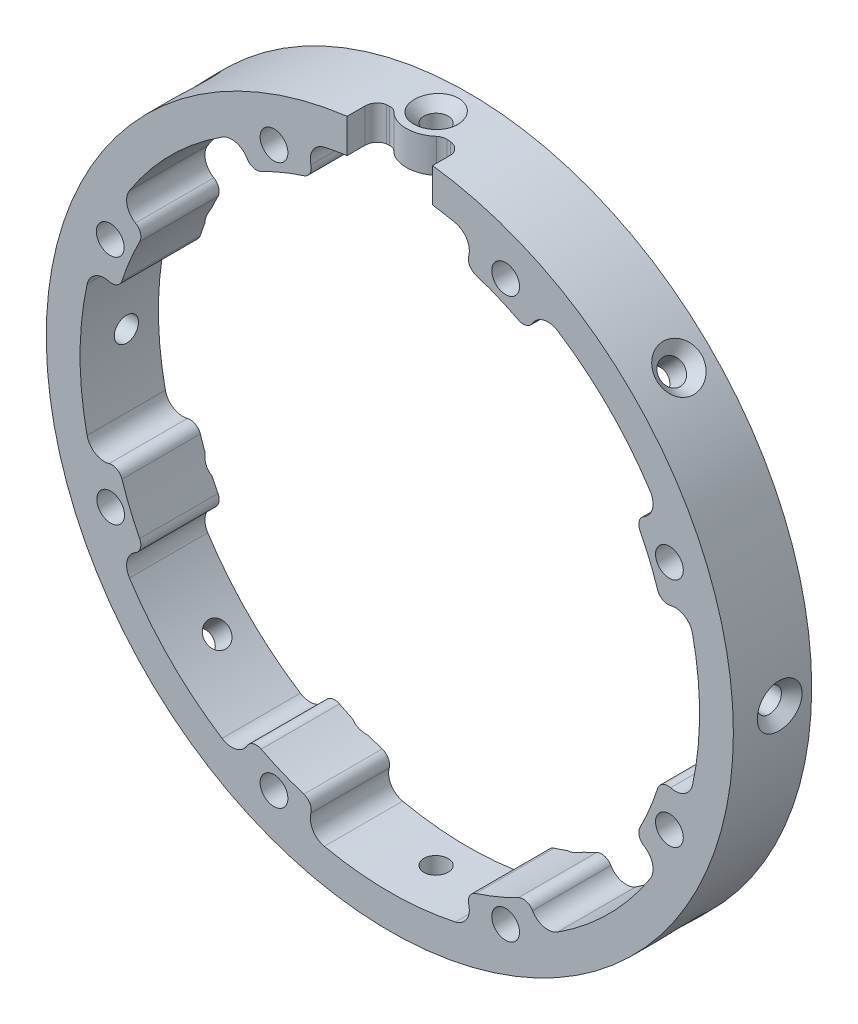
SolidWorks part; units mm, degrees
ref_plane "前视基准面" through (0, 0, 0) normal (0, 0, 1) x (1, 0, 0)
ref_plane "上视基准面" through (0, 0, 0) normal (0, 1, 0) x (1, 0, 0)
ref_plane "右视基准面" through (0, 0, 0) normal (1, 0, 0) x (0, 0, -1)
sketch "草图1" plane through (0, 0, 0) normal (0, 0, 1) x (1, 0, 0)
  line L0 (11.1292, 41.5348) -> (10.0939, 37.6711)
  line L17 (21.5, 37.2391) -> (19.5, 33.775)
  line L18 (-11.1292, 41.5348) -> (-10.0939, 37.6711)
  line L19 (37.2391, 21.5) -> (33.775, 19.5)
  line L20 (41.5348, 11.1292) -> (37.6711, 10.0939)
  line L21 (41.5348, -11.1292) -> (37.6711, -10.0939)
  line L22 (37.2391, -21.5) -> (33.775, -19.5)
  line L23 (21.5, -37.2391) -> (19.5, -33.775)
  line L24 (11.1292, -41.5348) -> (10.0939, -37.6711)
  line L25 (-11.1292, -41.5348) -> (-10.0939, -37.6711)
  line L26 (-21.5, -37.2391) -> (-19.5, -33.775)
  line L27 (-37.2391, -21.5) -> (-33.775, -19.5)
  line L28 (-41.5348, -11.1292) -> (-37.6711, -10.0939)
  line L29 (-41.5348, 11.1292) -> (-37.6711, 10.0939)
  line L30 (-37.2391, 21.5) -> (-33.775, 19.5)
  line L31 (-21.5, 37.2391) -> (-19.5, 33.775)
  circle A1 centre (0, 0) radius 48.25
  arc A3 (10.0939, 37.6711) -> (19.5, 33.775) centre (0, 0) cw
  arc A4 (11.1292, 41.5348) -> (-11.1292, 41.5348) centre (0, 0) ccw
  arc A21 (37.2391, 21.5) -> (21.5, 37.2391) centre (0, 0) ccw
  arc A22 (33.775, 19.5) -> (37.6711, 10.0939) centre (0, 0) cw
  arc A23 (41.5348, -11.1292) -> (41.5348, 11.1292) centre (0, 0) ccw
  arc A24 (37.6711, -10.0939) -> (33.775, -19.5) centre (0, 0) cw
  arc A25 (21.5, -37.2391) -> (37.2391, -21.5) centre (0, 0) ccw
  arc A26 (19.5, -33.775) -> (10.0939, -37.6711) centre (0, 0) cw
  arc A27 (-11.1292, -41.5348) -> (11.1292, -41.5348) centre (0, 0) ccw
  arc A28 (-10.0939, -37.6711) -> (-19.5, -33.775) centre (0, 0) cw
  arc A29 (-37.2391, -21.5) -> (-21.5, -37.2391) centre (0, 0) ccw
  arc A30 (-33.775, -19.5) -> (-37.6711, -10.0939) centre (0, 0) cw
  arc A31 (-41.5348, 11.1292) -> (-41.5348, -11.1292) centre (0, 0) ccw
  arc A32 (-37.6711, 10.0939) -> (-33.775, 19.5) centre (0, 0) cw
  arc A33 (-21.5, 37.2391) -> (-37.2391, 21.5) centre (0, 0) ccw
  arc A34 (-19.5, 33.775) -> (-10.0939, 37.6711) centre (0, 0) cw
  point P51 (0, 0)
  point P56 (0, 0)
  dimension "D1" = 8
  dimension "D2" = 43
  dimension "D3" = 96.5
extrude "凸台-拉伸1" add sketch "草图1" against normal blind 11
hole_wizard "M3 锥坑平头的锥孔2" positions "3D草图3" profile "草图4" countersink size "M3" standard "BSI" end condition through all
sketch3d "3D草图3"
  point P67 (34.1179, 34.1179, -6.5)
  point P76 (48.25, 0, -6.5)
  point P83 (34.1179, -34.1179, -6.5)
  point P85 (-34.1179, 34.1179, -6.5)
  point P87 (-34.1179, -34.1179, -6.5)
  point P96 (0, -48.25, -6.5)
  point P98 (0, 48.25, -6.5)
  point P105 (-48.25, 0, -6.5)
sketch "草图4" plane through (34.1179, 34.1179, -6.5) normal (0, 0, 1) x (-0.7071, 0.7071, 0)
  line L0 (0, 0) -> (0, 116.4858)
  line L1 (0, 116.4858) -> (1.7, 116.4858)
  line L2 (1.7, 116.4858) -> (1.7, 1.45)
  line L3 (1.7, 1.45) -> (3.15, 0)
  line L5 (3.15, 0) -> (0, 0)
  line L6 (-1.7, 1.45) -> (-3.15, 0) construction
  line L11 (0, -6.35) -> (0, 107.95) construction
  dimension "通孔孔直径" = 3.4
  dimension "通孔孔深度" = 116.4858
  dimension "近端锥形沉头孔直径" = 6.3
  dimension "近端锥形沉头孔角度" = 90
ref_plane "基准面1" through (0, 48.25, 0) normal (0, 1, 0) x (1, 0, 0)
sketch "草图7" plane through (0, 48.25, 0) normal (0, 1, 0) x (1, 0, 0)
  line L0 (-6, 0) -> (6, 0)
  line L1 (-48.25, 0) -> (48.25, 0) construction
  line L2 (6, 0) -> (6, 4)
  line L3 (6, 4) -> (3.3749, 4)
  line L5 (-6, 0) -> (-6, 4)
  line L6 (-6, 4) -> (-3.3749, 4)
  arc A1 (3.3749, 4) -> (-3.3749, 4) centre (0, 6.5) cw
extrude "切除-拉伸1" cut sketch "草图7" against normal up to next
sketch "草图9" plane through (0, 0, 0) normal (0, 0, 1) x (1, 0, 0)
  line L0 (0, 0) -> (0, 43) construction
  line L1 (0, 0) -> (16.264, 39.2649) construction
  circle A0 centre (0, 0) radius 42.5 construction
  circle A1 centre (16.264, 39.2649) radius 2
  arc A2 (3.3749, 42.8674) -> (-3.3749, 42.8674) centre (0, 0) ccw construction
  circle A3 centre (39.2649, 16.264) radius 2
  circle A4 centre (39.2649, -16.264) radius 2
  circle A5 centre (16.264, -39.2649) radius 2
  circle A6 centre (-16.264, -39.2649) radius 2
  circle A7 centre (-39.2649, -16.264) radius 2
  circle A8 centre (-39.2649, 16.264) radius 2
  circle A9 centre (-16.264, 39.2649) radius 2
  point P25 (0, 0)
  dimension "D1" = 85
  dimension "D3" = 4
  dimension "D2" = 22.5
  dimension "D4" = 8
hole_wizard "打孔尺寸(%根据十字)槽半沉头木螺钉的类型2" positions "3D草图4" profile "草图8" countersink size "M3.5" standard "GB" end condition up to next
sketch3d "3D草图4"
  point P13 (39.2649, 16.264, -11)
  point P19 (16.264, 39.2649, -11)
  point P21 (-16.264, 39.2649, -11)
  point P23 (39.2649, -16.264, -11)
  point P26 (-39.2649, 16.264, -11)
  point P28 (-39.2044, -16.264, -11)
  point P30 (-16.264, -39.2649, -11)
  point P32 (16.264, -39.2649, -11)
sketch "草图8" plane through (39.2649, 16.264, -11) normal (1, 0, 0) x (0, 1, 0)
  line L0 (0, 0) -> (0, 11)
  line L1 (0, 11) -> (1.95, 11)
  line L2 (1.95, 11) -> (1.95, 1.3)
  line L3 (1.95, 1.3) -> (3.25, 0)
  line L5 (3.25, 0) -> (0, 0)
  line L6 (-1.95, 1.3) -> (-3.25, 0) construction
  line L11 (0, -6.35) -> (0, 107.95) construction
  dimension "通孔孔直径" = 3.9
  dimension "通孔孔深度" = 11
  dimension "近端锥形沉头孔直径" = 6.5
  dimension "近端锥形沉头孔角度" = 90
fillet "圆角1" radius 2 32 edges at (-41.5348, -11.1292, -5.5) (-37.6711, -10.0939, -5.5) (-33.775, -19.5, -5.5) (-37.2391, -21.5, -5.5) (-21.5, -37.2391, -5.5) (-10.0939, -37.6711, -5.5) (-19.5, -33.775, -5.5) (-11.1292, -41.5348, -5.5) (11.1292, -41.5348, -5.5) (10.0939, -37.6711, -5.5) (19.5, -33.775, -5.5) (21.5, -37.2391, -5.5) (37.2391, -21.5, -5.5) (33.775, -19.5, -5.5) (37.6711, -10.0939, -5.5) (41.5348, -11.1292, -5.5) (41.5348, 11.1292, -5.5) (37.6711, 10.0939, -5.5) (33.775, 19.5, -5.5) (37.2391, 21.5, -5.5) (21.5, 37.2391, -5.5) (11.1292, 41.5348, -5.5) (10.0939, 37.6711, -5.5) (19.5, 33.775, -5.5) (-11.1292, 41.5348, -5.5) (-10.0939, 37.6711, -5.5) (-21.5, 37.2391, -5.5) (-19.5, 33.775, -5.5) (-37.2391, 21.5, -5.5) (-33.775, 19.5, -5.5) (-37.6711, 10.0939, -5.5) (-41.5348, 11.1292, -5.5)
fillet "圆角2" radius 1.5 4 edges at (-6, 45.2274, -4) (6, 45.2274, -4) (-3.3749, 45.4996, -4) (3.3749, 45.4996, -4)
sketch "草图10" plane through (0, 0, 0) normal (0, 0, 1) x (1, 0, 0)
  line L0 (6.5, 47.8755) -> (6.5, 43.0116)
  line L1 (-6.5, 43.0116) -> (-6.5, 47.8755)
  line L2 (-6, 42.5793) -> (-6, 47.8755)
  line L3 (6, 47.8755) -> (6, 42.5793)
  line L4 (-6, 42.5793) -> (-6, 47.8755)
  line L5 (6, 47.8755) -> (6, 42.5793)
  arc A0 (9.1956, 42.517) -> (6.5, 43.0116) centre (0, 0) ccw
  arc A1 (11.0819, 39.4264) -> (9.1956, 42.517) centre (8.6671, 40.0735) ccw
  arc A2 (11.0819, 39.4264) -> (12.0724, 37.6099) centre (12.5308, 39.0382) ccw
  arc A3 (18.0578, 35.1307) -> (12.0724, 37.6099) centre (0, 0) ccw
  arc A4 (18.0578, 35.1307) -> (20.0426, 35.7148) centre (18.7435, 36.4648) ccw
  arc A5 (23.5618, 36.5663) -> (20.0426, 35.7148) centre (22.2076, 34.4648) ccw
  arc A6 (36.5663, 23.5618) -> (23.5618, 36.5663) centre (0, 0) ccw
  arc A7 (35.7148, 20.0426) -> (36.5663, 23.5618) centre (34.4648, 22.2076) ccw
  arc A8 (35.7148, 20.0426) -> (35.1307, 18.0578) centre (36.4648, 18.7435) ccw
  arc A9 (37.6099, 12.0724) -> (35.1307, 18.0578) centre (0, 0) ccw
  arc A10 (37.6099, 12.0724) -> (39.4264, 11.0819) centre (39.0382, 12.5308) ccw
  arc A11 (42.517, 9.1956) -> (39.4264, 11.0819) centre (40.0735, 8.6671) ccw
  arc A12 (42.517, -9.1956) -> (42.517, 9.1956) centre (0, 0) ccw
  arc A13 (39.4264, -11.0819) -> (42.517, -9.1956) centre (40.0735, -8.6671) ccw
  arc A14 (39.4264, -11.0819) -> (37.6099, -12.0724) centre (39.0382, -12.5308) ccw
  arc A15 (35.1307, -18.0578) -> (37.6099, -12.0724) centre (0, 0) ccw
  arc A16 (35.1307, -18.0578) -> (35.7148, -20.0426) centre (36.4648, -18.7435) ccw
  arc A17 (36.5663, -23.5618) -> (35.7148, -20.0426) centre (34.4648, -22.2076) ccw
  arc A18 (23.5618, -36.5663) -> (36.5663, -23.5618) centre (0, 0) ccw
  arc A19 (20.0426, -35.7148) -> (23.5618, -36.5663) centre (22.2076, -34.4648) ccw
  arc A20 (20.0426, -35.7148) -> (18.0578, -35.1307) centre (18.7435, -36.4648) ccw
  arc A21 (12.0724, -37.6099) -> (18.0578, -35.1307) centre (0, 0) ccw
  arc A22 (12.0724, -37.6099) -> (11.0819, -39.4264) centre (12.5308, -39.0382) ccw
  arc A23 (9.1956, -42.517) -> (11.0819, -39.4264) centre (8.6671, -40.0735) ccw
  arc A24 (-9.1956, -42.517) -> (9.1956, -42.517) centre (0, 0) ccw
  arc A25 (-11.0819, -39.4264) -> (-9.1956, -42.517) centre (-8.6671, -40.0735) ccw
  arc A26 (-11.0819, -39.4264) -> (-12.0724, -37.6099) centre (-12.5308, -39.0382) ccw
  arc A27 (-18.0578, -35.1307) -> (-12.0724, -37.6099) centre (0, 0) ccw
  arc A28 (-18.0578, -35.1307) -> (-20.0426, -35.7148) centre (-18.7435, -36.4648) ccw
  arc A29 (-23.5618, -36.5663) -> (-20.0426, -35.7148) centre (-22.2076, -34.4648) ccw
  arc A30 (-36.5663, -23.5618) -> (-23.5618, -36.5663) centre (0, 0) ccw
  arc A31 (-35.7148, -20.0426) -> (-36.5663, -23.5618) centre (-34.4648, -22.2076) ccw
  arc A32 (-35.7148, -20.0426) -> (-35.1307, -18.0578) centre (-36.4648, -18.7435) ccw
  arc A33 (-37.6099, -12.0724) -> (-35.1307, -18.0578) centre (0, 0) ccw
  arc A34 (-37.6099, -12.0724) -> (-39.4264, -11.0819) centre (-39.0382, -12.5308) ccw
  arc A35 (-42.517, -9.1956) -> (-39.4264, -11.0819) centre (-40.0735, -8.6671) ccw
  arc A36 (-42.517, 9.1956) -> (-42.517, -9.1956) centre (0, 0) ccw
  arc A37 (-39.4264, 11.0819) -> (-42.517, 9.1956) centre (-40.0735, 8.6671) ccw
  arc A38 (-39.4264, 11.0819) -> (-37.6099, 12.0724) centre (-39.0382, 12.5308) ccw
  arc A39 (-35.1307, 18.0578) -> (-37.6099, 12.0724) centre (0, 0) ccw
  arc A40 (-35.1307, 18.0578) -> (-35.7148, 20.0426) centre (-36.4648, 18.7435) ccw
  arc A41 (-36.5663, 23.5618) -> (-35.7148, 20.0426) centre (-34.4648, 22.2076) ccw
  arc A42 (-23.5618, 36.5663) -> (-36.5663, 23.5618) centre (0, 0) ccw
  arc A43 (-20.0426, 35.7148) -> (-23.5618, 36.5663) centre (-22.2076, 34.4648) ccw
  arc A44 (-20.0426, 35.7148) -> (-18.0578, 35.1307) centre (-18.7435, 36.4648) ccw
  arc A45 (-12.0724, 37.6099) -> (-18.0578, 35.1307) centre (0, 0) ccw
  arc A46 (-12.0724, 37.6099) -> (-11.0819, 39.4264) centre (-12.5308, 39.0382) ccw
  arc A47 (-9.1956, 42.517) -> (-11.0819, 39.4264) centre (-8.6671, 40.0735) ccw
  arc A48 (-6.5, 43.0116) -> (-9.1956, 42.517) centre (0, 0) ccw
  arc A49 (-6.5, 43.0116) -> (6.5322, 43.0067) centre (0, 0) cw
  arc A50 (-37.1339, -11.9195) -> (-34.686, -17.8292) centre (0, 0) ccw
  arc A51 (-37.1339, -11.9195) -> (-39.5558, -10.5989) centre (-39.0382, -12.5308) ccw
  arc A52 (-42.0283, -9.0899) -> (-39.5558, -10.5989) centre (-40.0735, -8.6671) ccw
  arc A53 (-42.0283, 9.0899) -> (-42.0283, -9.0899) centre (0, 0) ccw
  arc A54 (-39.5558, 10.5989) -> (-42.0283, 9.0899) centre (-40.0735, 8.6671) ccw
  arc A55 (-39.5558, 10.5989) -> (-37.1339, 11.9195) centre (-39.0382, 12.5308) ccw
  arc A56 (-34.686, 17.8292) -> (-37.1339, 11.9195) centre (0, 0) ccw
  arc A57 (-34.686, 17.8292) -> (-35.4648, 20.4756) centre (-36.4648, 18.7435) ccw
  arc A58 (-36.146, 23.2909) -> (-35.4648, 20.4756) centre (-34.4648, 22.2076) ccw
  arc A59 (-23.2909, 36.146) -> (-36.146, 23.2909) centre (0, 0) ccw
  arc A60 (-20.4756, 35.4648) -> (-23.2909, 36.146) centre (-22.2076, 34.4648) ccw
  arc A61 (-20.4756, 35.4648) -> (-17.8292, 34.686) centre (-18.7435, 36.4648) ccw
  arc A62 (-11.9195, 37.1339) -> (-17.8292, 34.686) centre (0, 0) ccw
  arc A63 (-11.9195, 37.1339) -> (-10.5989, 39.5558) centre (-12.5308, 39.0382) ccw
  arc A64 (-9.0899, 42.0283) -> (-10.5989, 39.5558) centre (-8.6671, 40.0735) ccw
  arc A65 (-6, 42.5793) -> (-9.0899, 42.0283) centre (0, 0) ccw
  arc A66 (-6, 47.8755) -> (6, 47.8755) centre (0, 0) ccw
  arc A67 (9.0899, 42.0283) -> (6, 42.5793) centre (0, 0) ccw
  arc A68 (10.5989, 39.5558) -> (9.0899, 42.0283) centre (8.6671, 40.0735) ccw
  arc A69 (10.5989, 39.5558) -> (11.9195, 37.1339) centre (12.5308, 39.0382) ccw
  arc A70 (17.8292, 34.686) -> (11.9195, 37.1339) centre (0, 0) ccw
  arc A71 (17.8292, 34.686) -> (20.4756, 35.4648) centre (18.7435, 36.4648) ccw
  arc A72 (23.2909, 36.146) -> (20.4756, 35.4648) centre (22.2076, 34.4648) ccw
  arc A73 (36.146, 23.2909) -> (23.2909, 36.146) centre (0, 0) ccw
  arc A74 (35.4648, 20.4756) -> (36.146, 23.2909) centre (34.4648, 22.2076) ccw
  arc A75 (35.4648, 20.4756) -> (34.686, 17.8292) centre (36.4648, 18.7435) ccw
  arc A76 (37.1339, 11.9195) -> (34.686, 17.8292) centre (0, 0) ccw
  arc A77 (37.1339, 11.9195) -> (39.5558, 10.5989) centre (39.0382, 12.5308) ccw
  arc A78 (42.0283, 9.0899) -> (39.5558, 10.5989) centre (40.0735, 8.6671) ccw
  arc A79 (42.0283, -9.0899) -> (42.0283, 9.0899) centre (0, 0) ccw
  arc A80 (39.5558, -10.5989) -> (42.0283, -9.0899) centre (40.0735, -8.6671) ccw
  arc A81 (39.5558, -10.5989) -> (37.1339, -11.9195) centre (39.0382, -12.5308) ccw
  arc A82 (34.686, -17.8292) -> (37.1339, -11.9195) centre (0, 0) ccw
  arc A83 (34.686, -17.8292) -> (35.4648, -20.4756) centre (36.4648, -18.7435) ccw
  arc A84 (36.146, -23.2909) -> (35.4648, -20.4756) centre (34.4648, -22.2076) ccw
  arc A85 (23.2909, -36.146) -> (36.146, -23.2909) centre (0, 0) ccw
  arc A86 (20.4756, -35.4648) -> (23.2909, -36.146) centre (22.2076, -34.4648) ccw
  arc A87 (20.4756, -35.4648) -> (17.8292, -34.686) centre (18.7435, -36.4648) ccw
  arc A88 (11.9195, -37.1339) -> (17.8292, -34.686) centre (0, 0) ccw
  arc A89 (11.9195, -37.1339) -> (10.5989, -39.5558) centre (12.5308, -39.0382) ccw
  arc A90 (9.0899, -42.0283) -> (10.5989, -39.5558) centre (8.6671, -40.0735) ccw
  arc A91 (-9.0899, -42.0283) -> (9.0899, -42.0283) centre (0, 0) ccw
  arc A92 (-10.5989, -39.5558) -> (-9.0899, -42.0283) centre (-8.6671, -40.0735) ccw
  arc A93 (-10.5989, -39.5558) -> (-11.9195, -37.1339) centre (-12.5308, -39.0382) ccw
  arc A94 (-17.8292, -34.686) -> (-11.9195, -37.1339) centre (0, 0) ccw
  arc A95 (-17.8292, -34.686) -> (-20.4756, -35.4648) centre (-18.7435, -36.4648) ccw
  arc A96 (-23.2909, -36.146) -> (-20.4756, -35.4648) centre (-22.2076, -34.4648) ccw
  arc A97 (-36.146, -23.2909) -> (-23.2909, -36.146) centre (0, 0) ccw
  arc A98 (-35.4648, -20.4756) -> (-36.146, -23.2909) centre (-34.4648, -22.2076) ccw
  arc A99 (-35.4648, -20.4756) -> (-34.686, -17.8292) centre (-36.4648, -18.7435) ccw
  arc A100 (-37.1339, -11.9195) -> (-34.686, -17.8292) centre (0, 0) ccw
  arc A101 (-37.1339, -11.9195) -> (-39.5558, -10.5989) centre (-39.0382, -12.5308) ccw
  arc A102 (-42.0283, -9.0899) -> (-39.5558, -10.5989) centre (-40.0735, -8.6671) ccw
  arc A103 (-42.0283, 9.0899) -> (-42.0283, -9.0899) centre (0, 0) ccw
  arc A104 (-39.5558, 10.5989) -> (-42.0283, 9.0899) centre (-40.0735, 8.6671) ccw
  arc A105 (-39.5558, 10.5989) -> (-37.1339, 11.9195) centre (-39.0382, 12.5308) ccw
  arc A106 (-34.686, 17.8292) -> (-37.1339, 11.9195) centre (0, 0) ccw
  arc A107 (-34.686, 17.8292) -> (-35.4648, 20.4756) centre (-36.4648, 18.7435) ccw
  arc A108 (-36.146, 23.2909) -> (-35.4648, 20.4756) centre (-34.4648, 22.2076) ccw
  arc A109 (-23.2909, 36.146) -> (-36.146, 23.2909) centre (0, 0) ccw
  arc A110 (-20.4756, 35.4648) -> (-23.2909, 36.146) centre (-22.2076, 34.4648) ccw
  arc A111 (-20.4756, 35.4648) -> (-17.8292, 34.686) centre (-18.7435, 36.4648) ccw
  arc A112 (-11.9195, 37.1339) -> (-17.8292, 34.686) centre (0, 0) ccw
  arc A113 (-11.9195, 37.1339) -> (-10.5989, 39.5558) centre (-12.5308, 39.0382) ccw
  arc A114 (-9.0899, 42.0283) -> (-10.5989, 39.5558) centre (-8.6671, 40.0735) ccw
  arc A115 (-6, 42.5793) -> (-9.0899, 42.0283) centre (0, 0) ccw
  arc A116 (-6, 47.8755) -> (6, 47.8755) centre (0, 0) ccw
  arc A117 (9.0899, 42.0283) -> (6, 42.5793) centre (0, 0) ccw
  arc A118 (10.5989, 39.5558) -> (9.0899, 42.0283) centre (8.6671, 40.0735) ccw
  arc A119 (10.5989, 39.5558) -> (11.9195, 37.1339) centre (12.5308, 39.0382) ccw
  arc A120 (17.8292, 34.686) -> (11.9195, 37.1339) centre (0, 0) ccw
  arc A121 (17.8292, 34.686) -> (20.4756, 35.4648) centre (18.7435, 36.4648) ccw
  arc A122 (23.2909, 36.146) -> (20.4756, 35.4648) centre (22.2076, 34.4648) ccw
  arc A123 (36.146, 23.2909) -> (23.2909, 36.146) centre (0, 0) ccw
  arc A124 (35.4648, 20.4756) -> (36.146, 23.2909) centre (34.4648, 22.2076) ccw
  arc A125 (35.4648, 20.4756) -> (34.686, 17.8292) centre (36.4648, 18.7435) ccw
  arc A126 (37.1339, 11.9195) -> (34.686, 17.8292) centre (0, 0) ccw
  arc A127 (37.1339, 11.9195) -> (39.5558, 10.5989) centre (39.0382, 12.5308) ccw
  arc A128 (42.0283, 9.0899) -> (39.5558, 10.5989) centre (40.0735, 8.6671) ccw
  arc A129 (42.0283, -9.0899) -> (42.0283, 9.0899) centre (0, 0) ccw
  arc A130 (39.5558, -10.5989) -> (42.0283, -9.0899) centre (40.0735, -8.6671) ccw
  arc A131 (39.5558, -10.5989) -> (37.1339, -11.9195) centre (39.0382, -12.5308) ccw
  arc A132 (34.686, -17.8292) -> (37.1339, -11.9195) centre (0, 0) ccw
  arc A133 (34.686, -17.8292) -> (35.4648, -20.4756) centre (36.4648, -18.7435) ccw
  arc A134 (36.146, -23.2909) -> (35.4648, -20.4756) centre (34.4648, -22.2076) ccw
  arc A135 (23.2909, -36.146) -> (36.146, -23.2909) centre (0, 0) ccw
  arc A136 (20.4756, -35.4648) -> (23.2909, -36.146) centre (22.2076, -34.4648) ccw
  arc A137 (20.4756, -35.4648) -> (17.8292, -34.686) centre (18.7435, -36.4648) ccw
  arc A138 (11.9195, -37.1339) -> (17.8292, -34.686) centre (0, 0) ccw
  arc A139 (11.9195, -37.1339) -> (10.5989, -39.5558) centre (12.5308, -39.0382) ccw
  arc A140 (9.0899, -42.0283) -> (10.5989, -39.5558) centre (8.6671, -40.0735) ccw
  arc A141 (-9.0899, -42.0283) -> (9.0899, -42.0283) centre (0, 0) ccw
  arc A142 (-10.5989, -39.5558) -> (-9.0899, -42.0283) centre (-8.6671, -40.0735) ccw
  arc A143 (-10.5989, -39.5558) -> (-11.9195, -37.1339) centre (-12.5308, -39.0382) ccw
  arc A144 (-17.8292, -34.686) -> (-11.9195, -37.1339) centre (0, 0) ccw
  arc A145 (-17.8292, -34.686) -> (-20.4756, -35.4648) centre (-18.7435, -36.4648) ccw
  arc A146 (-23.2909, -36.146) -> (-20.4756, -35.4648) centre (-22.2076, -34.4648) ccw
  arc A147 (-36.146, -23.2909) -> (-23.2909, -36.146) centre (0, 0) ccw
  arc A148 (-35.4648, -20.4756) -> (-36.146, -23.2909) centre (-34.4648, -22.2076) ccw
  arc A149 (-35.4648, -20.4756) -> (-34.686, -17.8292) centre (-36.4648, -18.7435) ccw
  dimension "D1" = 0
  dimension "D2" = 0.5
extrude "切除-拉伸2" cut sketch "草图10" against normal through all contours A149 A148 A147 A146 A145 A144 A143 A142 A141 A140 A139 A138 A137 A136 A135 A134 A133 A132 A131 A130 A129 A128 A127 A126 A125 A124 A123 A122 A121 A120 A119 A118 A117 L5 A49 L4 A115 A114 A113 A112 A111 A110 A109 A108 A107 A106 A105 A104 A103 A102 A101 | A148 A149 A100 A101 A102 A103 A104 A105 A106 A107 A108 A109 A110 A111 A112 A113 A114 A115 L4 A49 A48 A47 A46 A45 A44 A43 A42 A41 A40 A39 A38 A37 A36 A35 A34 A33 A32 A31 A30 A29 A28 A27 A26 A25 A24 A23 A22 A21 A20 A19 A18 region at (6.4977, 42.8878, 0) region at (0, 0.0474, 0)
